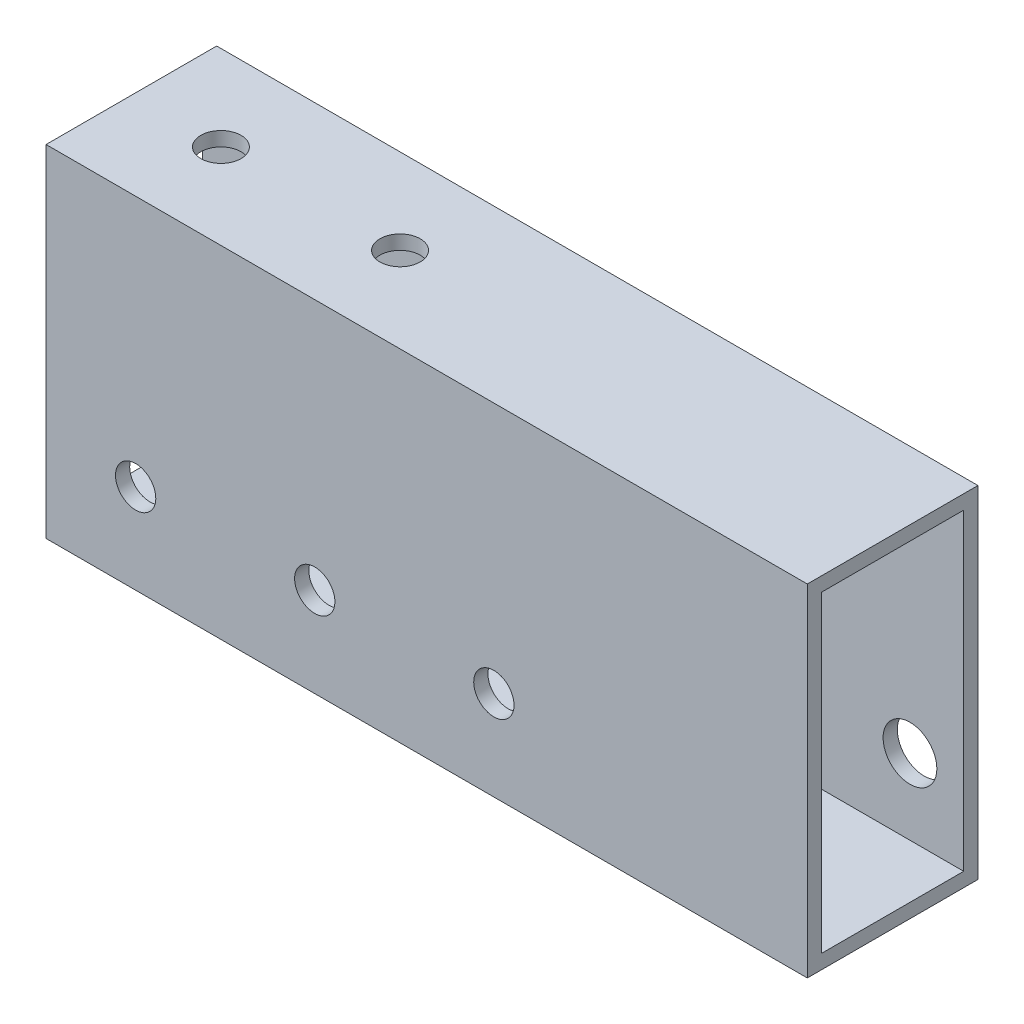
SolidWorks part; units mm, degrees
material "6063-T6"
ref_plane "Front Plane" through (0, 0, 0) normal (0, 0, 1) x (1, 0, 0)
ref_plane "Top Plane" through (0, 0, 0) normal (0, 1, 0) x (1, 0, 0)
ref_plane "Right Plane" through (0, 0, 0) normal (1, 0, 0) x (0, 0, -1)
ref_plane "Plane1" through (100, 0, 0) normal (1, 0, 0) x (0, 0, -1)
sketch "Sketch1" plane through (0, 0, 0) normal (1, 0, 0) x (0, 0, -1)
  line L0 (19.05, -38.1) -> (0, -19.05) construction
  line L1 (-19.05, 38.1) -> (19.05, 38.1)
  line L2 (-19.05, 38.1) -> (-19.05, -38.1)
  line L3 (-19.05, -38.1) -> (19.05, -38.1)
  line L4 (19.05, 38.1) -> (19.05, -38.1)
  line L5 (-19.05, 38.1) -> (19.05, -38.1) construction
  line L6 (-19.05, -38.1) -> (19.05, 38.1) construction
  line L7 (0, 55) -> (0, -55) construction
  point P0 (0, 0)
  point P6 (0, -19.05)
  dimension "D1" = 38.1
  dimension "D2" = 76.2
  dimension "D3" = 45
extrude "Extrude-Thin1" add sketch "Sketch1" along normal offset from surface 30 and the other way blind 40 thin up to plane "Plane1" offset beyond the face yes thin type one direction reverse wall 3.175
hole_wizard "M8 Clearance Hole2" positions "Sketch2" profile "Sketch3" hole size "M8" standard "ANSI Metric" end condition through all
sketch "Sketch2" plane through (0, 0, -19.05) normal (0, 0, -1) x (-1, 0, 0)
  line L0 (-20, -18.1) -> (20, -18.1)
  line L1 (0, 55) -> (0, -55) construction
  line L2 (40, -38.1) -> (-130, -38.1) construction
  line L3 (-20, -18.1) -> (-60, -18.1)
  point P0 (20, -18.1)
  point P2 (-20, -18.1)
  point P9 (0, -18.1)
  point P20 (-60, -18.1)
  dimension "D1" = 40
  dimension "D2" = 20
sketch "Sketch3" plane through (-20, -18.1, -19.05) normal (1, 0, 0) x (0, 1, 0)
  line L0 (0, 0) -> (0, 38.1)
  line L1 (0, 38.1) -> (4.5, 38.1)
  line L2 (4.5, 38.1) -> (4.5, 0)
  line L5 (4.5, 0) -> (0, 0)
  line L11 (0, -6.35) -> (0, 107.95) construction
  dimension "Thru Hole Dia." = 9
  dimension "Thru Hole Depth" = 38.1
hole_wizard "M8 Clearance Hole3" positions "Sketch9" profile "Sketch10" hole size "M8" standard "ANSI Metric" end condition through all
sketch "Sketch9" plane through (0, -38.1, 0) normal (0, -1, 0) x (-1, 0, 0)
  line L0 (-20, 0) -> (20, 0)
  line L2 (-20, 19.05) -> (20, 19.05) construction
  point P1 (-20, 0)
  point P2 (20, 0)
sketch "Sketch10" plane through (20, -38.1, 0) normal (1, 0, 0) x (0, 0, -1)
  line L0 (0, 0) -> (0, 76.2)
  line L1 (0, 76.2) -> (4.5, 76.2)
  line L2 (4.5, 76.2) -> (4.5, 0)
  line L5 (4.5, 0) -> (0, 0)
  line L11 (0, -6.35) -> (0, 107.95) construction
  dimension "Thru Hole Dia." = 9
  dimension "Thru Hole Depth" = 76.2
hole_wizard "Ø12.0 (12) Diameter Hole1" positions "Sketch6" profile "Sketch7" hole size "Ø12.0" standard "ANSI Metric" end condition up to next
sketch "Sketch6" plane through (0, 0, -19.05) normal (0, 0, -1) x (-1, 0, 0)
  line L0 (-82, -18.1) -> (-118, -18.1)
  line L6 (-20, -18.1) -> (20, -18.1) construction
  line L7 (-100, 20.955) -> (-100, -20.955) construction
  point P0 (-118, -18.1)
  point P2 (-82, -18.1)
  point P23 (-100, -18.1)
  dimension "D1" = 36
sketch "Sketch7" plane through (118, -18.1, -19.05) normal (1, 0, 0) x (0, 1, 0)
  line L0 (0, 0) -> (0, 3.175)
  line L1 (0, 3.175) -> (6, 3.175)
  line L2 (6, 3.175) -> (6, 0)
  line L5 (6, 0) -> (0, 0)
  line L11 (0, -6.35) -> (0, 107.95) construction
  dimension "Thru Hole Dia." = 12
  dimension "Thru Hole Depth" = 3.175
